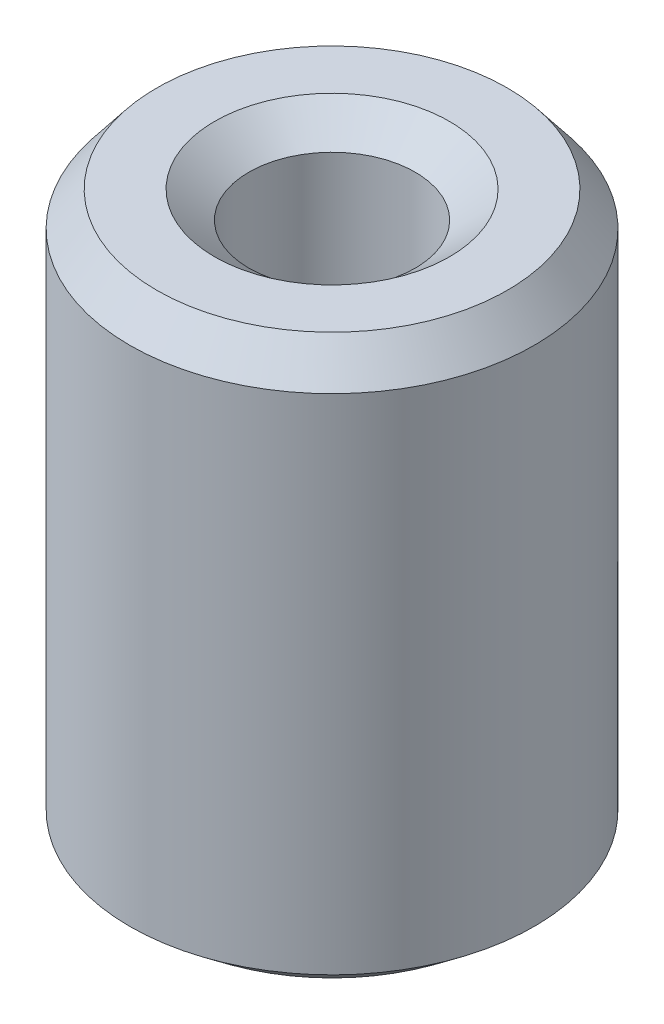
SolidWorks part; units mm, degrees
ref_plane "Front Plane" through (0, 0, 0) normal (0, 0, 1) x (1, 0, 0)
ref_plane "Top Plane" through (0, 0, 0) normal (0, 1, 0) x (1, 0, 0)
ref_plane "Right Plane" through (0, 0, 0) normal (1, 0, 0) x (0, 0, -1)
sketch "Sketch1" plane through (0, 0, 0) normal (0, 1, 0) x (1, 0, 0)
  circle A0 centre (0, 0) radius 7.5
  dimension "SLEEVE_OD" = 15
extrude "Boss-Extrude1" add sketch "Sketch1" along normal blind 20.9359
sketch "Sketch2" plane through (0, 0, 0) normal (0, 1, 0) x (1, 0, 0)
  circle A0 centre (0, 0) radius 3.0862
  dimension "BORE_D" = 6.1724
extrude "Cut-Extrude1" cut sketch "Sketch2" along normal through all
chamfer "Chamfer1" distance 1.269 angle 38.169 4 edges at (0, 20.9359, 3.0862) (0, 0, 3.0862) (0, 0, 7.5) (0, 20.9359, 7.5) first distance on face at (0, 20.9359, 3.0862) first distance on face at (0, 0, 3.0862) first distance on face at (0, 20.9359, 7.5)
